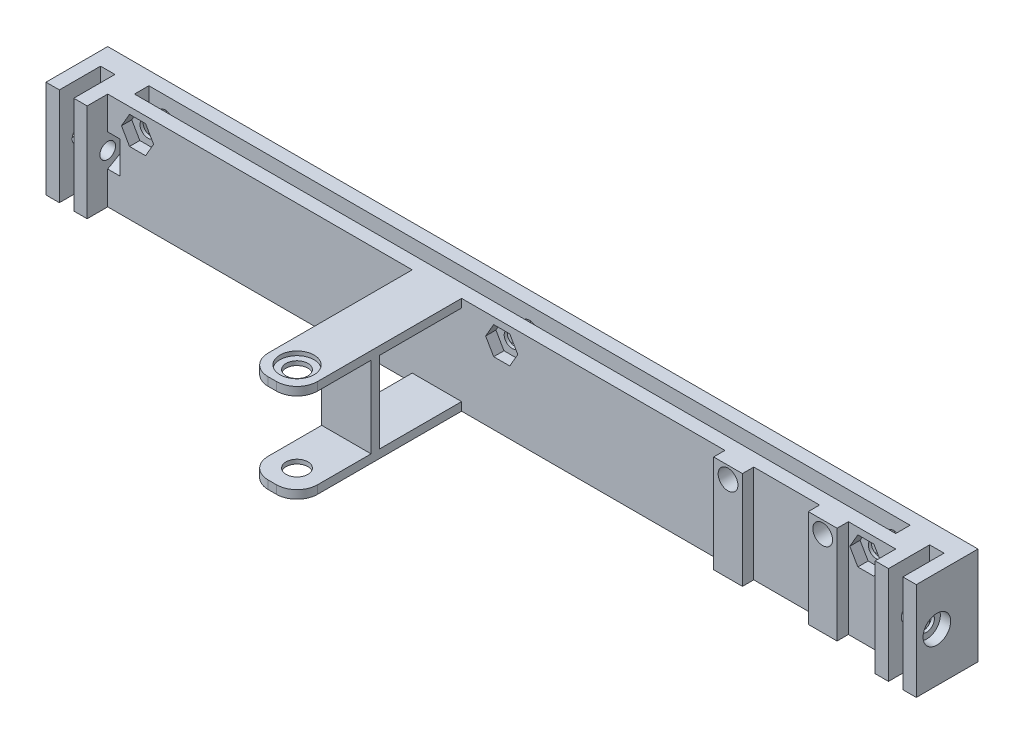
SolidWorks part; units mm, degrees
ref_plane "Front Plane" through (0, 0, 0) normal (1, 0, 0) x (0, 1, 0)
ref_plane "Top Plane" through (0, 0, 0) normal (0, 0, 1) x (0, 1, 0)
ref_plane "Right Plane" through (0, 0, 0) normal (0, 1, 0) x (-1, 0, 0)
sketch "Sketch2" plane through (0, 0, 0) normal (0, 0, 1) x (0, 1, 0)
  line L1 (-71.25, 0) -> (-95, 0)
  line L2 (-71.25, 0) -> (-71.25, 12)
  line L3 (-71.25, 12) -> (-95, 12)
  line L4 (-95, 0) -> (-95, 12)
extrude "Boss-Extrude1" add sketch "Sketch2" along normal blind 10
sketch "Sketch3" plane through (0, 0, 10) normal (0, 0, 1) x (1, 0, 0)
  line L1 (-12, -71.25) -> (0, -71.25)
  line L2 (-12, -71.25) -> (-12, -73.275)
  line L3 (-12, -73.275) -> (0, -73.275)
  line L4 (0, -71.25) -> (0, -73.275)
  line L6 (-12, -73.275) -> (0, -73.275) construction
  dimension "D1" = 2.025
extrude "Boss-Extrude2" add sketch "Sketch3" along normal blind 40
fillet "Fillet1" radius 5 2 edges at (0, -72.2625, 50) (-12, -72.2625, 50)
ref_plane "Plane1" through (0, -83.125, 0) normal (0, 1, 0) x (1, 0, 0)
mirror "Mirror1" about plane through (0, -83.125, 0) normal (0, 1, 0) of "Fillet1", "Boss-Extrude2"
sketch "Sketch5" plane through (0, -95, 0) normal (0, -1, 0) x (1, 0, 0)
  line L1 (-6, 50) -> (-12, 50)
  line L2 (-6, 50) -> (-6, 44)
  line L3 (-6, 44) -> (-12, 44)
  line L4 (-12, 50) -> (-12, 44)
  line L5 (-5, 50) -> (-7, 50) construction
  line L6 (-12, 45) -> (-12, 0) construction
  circle A0 centre (-6, 44) radius 2.65
  dimension "D2" = 5.3
  dimension "D1" = 6
extrude "Cut-Extrude1" cut sketch "Sketch5" against normal through all contours A0
sketch "Sketch6" plane through (0, -95, 0) normal (0, -1, 0) x (1, 0, 0)
  line L1 (-6, 50) -> (-12, 50)
  line L2 (-6, 50) -> (-6, 44)
  line L3 (-6, 44) -> (-12, 44)
  line L4 (-12, 50) -> (-12, 44)
  line L6 (-5, 50) -> (-7, 50) construction
  line L7 (-12, 45) -> (-12, 0) construction
  circle A0 centre (-6, 44) radius 4.15
  dimension "D1" = 6
  dimension "D2" = 8.3
extrude "Cut-Extrude2" cut sketch "Sketch6" against normal blind 1 contours A0
mirror "Mirror2" about plane through (0, -83.125, 0) normal (0, 1, 0) of "Cut-Extrude2"
sketch "Sketch7" plane through (0, 0, 0) normal (0, 0, -1) x (1, 0, 0)
  line L1 (-6, 95) -> (-96, 95)
  line L2 (-6, 95) -> (-6, 71.25)
  line L3 (-6, 71.25) -> (-96, 71.25)
  line L4 (-96, 95) -> (-96, 71.25)
  line L5 (-6, 95) -> (115.5, 95)
  line L6 (-6, 95) -> (-6, 71.25)
  line L7 (-6, 71.25) -> (115.5, 71.25)
  line L8 (115.5, 95) -> (115.5, 71.25)
  line L10 (-12, 95) -> (0, 95) construction
  line L11 (0, 71.25) -> (-12, 71.25) construction
  line M20 (0, 71.25) -> (0, 95)
  line M22 (-12, 95) -> (-12, 71.25)
  dimension "D1" = 90
  dimension "D2" = 121.5
extrude "Boss-Extrude3" add sketch "Sketch7" against normal blind 10 contours L1 L4 L3 M22 | L8 L5 L7 M20 region at (-54, -83.125, 0) region at (57.75, -83.125, 0)
sketch "Sketch8" plane through (0, 0, 10) normal (0, 0, 1) x (1, 0, 0)
  line L1 (115.5, -71.25) -> (105.5, -71.25)
  line L2 (115.5, -71.25) -> (115.5, -95)
  line L3 (115.5, -95) -> (105.5, -95)
  line L4 (105.5, -71.25) -> (105.5, -95)
  line L6 (-96, -71.25) -> (-86, -71.25)
  line L7 (-96, -71.25) -> (-96, -95)
  line L8 (-96, -95) -> (-86, -95)
  line L9 (-86, -71.25) -> (-86, -95)
  dimension "D1" = 10
  dimension "D2" = 10
extrude "Boss-Extrude4" add sketch "Sketch8" along normal blind 5
sketch "Sketch10" plane through (-12, 0, 0) normal (-1, 0, 0) x (0, -1, 0)
  line L0 (95, 45) -> (95, 10) construction
  line L1 (71.25, 10) -> (95, 10)
  line L2 (71.25, 10) -> (71.25, 12)
  line L3 (71.25, 12) -> (95, 12)
  line L4 (95, 10) -> (95, 12)
  dimension "D1" = 2
extrude "Boss-Extrude5" [suppressed] add sketch "Sketch10" along normal blind 24
sketch "Sketch18" plane through (0, -71.25, 0) normal (0, 1, 0) x (-1, 0, 0)
  line L1 (0, 10) -> (12, 10)
  line L2 (0, 10) -> (0, 30)
  line L3 (0, 30) -> (12, 30)
  line L4 (12, 10) -> (12, 30)
  line L5 (12, 45) -> (12, 10) construction
  line L6 (0, 30) -> (12, 30)
  line L7 (0, 30) -> (0, 32)
  line L8 (0, 32) -> (12, 32)
  line L9 (12, 30) -> (12, 32)
  dimension "D1" = 20
  dimension "D2" = 2
extrude "Boss-Extrude7" add sketch "Sketch18" against normal through all contours L7 L6 L9 L8
sketch "Sketch11" plane through (0, -71.25, 0) normal (0, 1, 0) x (-1, 0, 0)
  line L1 (86, 0) -> (-105.5, 0)
  line L2 (86, 0) -> (86, 10)
  line L3 (86, 10) -> (-105.5, 10)
  line L4 (-105.5, 0) -> (-105.5, 10)
  line L5 (82.75, 6.75) -> (-102.25, 6.75)
  line L6 (-102.25, 3.25) -> (-102.25, 6.75)
  line L7 (82.75, 3.25) -> (-102.25, 3.25)
  line L8 (82.75, 3.25) -> (82.75, 6.75)
  line L12 (96, 0) -> (86, 0)
  line L13 (96, 0) -> (96, 10)
  line L14 (96, 10) -> (86, 10)
  line L15 (86, 0) -> (86, 10)
  dimension "D1" = 3.25
extrude "Cut-Extrude3" cut sketch "Sketch11" against normal blind 10 contours L7 L8 L5 L6 region at (9.75, -71.25, 5)
mirror "Mirror3" about plane through (0, -83.125, 0) normal (0, 1, 0) of "Cut-Extrude3"
sketch "Sketch12" plane through (0, 0, 10) normal (0, 0, 1) x (1, 0, 0)
  line L1 (-86, -71.25) -> (-78.75, -71.25)
  line L2 (-86, -71.25) -> (-86, -76.25)
  line L3 (-86, -76.25) -> (-78.75, -76.25)
  line L4 (-78.75, -71.25) -> (-78.75, -76.25)
  circle A0 centre (-78.75, -76.25) radius 1.9
  circle A1 centre (-78.75, -76.25) radius 3.15
  dimension "D3" = 3.8
  dimension "D4" = 6.3
  dimension "D1" = 7.25
extrude "Cut-Extrude4" cut sketch "Sketch12" against normal through all and the other way through all contours A0
sketch "Sketch15" plane through (0, 0, 0) normal (0, 0, 1) x (1, 0, 0)
  circle A0 centre (-78.75, -76.25) radius 3.35
  dimension "D1" = 6.7
extrude "Cut-Extrude5" cut sketch "Sketch15" along normal blind 2.5
sketch "Sketch16" plane through (0, 0, 10) normal (0, 0, 1) x (1, 0, 0)
  line L0 (-82.6541, -76.25) -> (-80.7021, -79.6311)
  line L1 (-82.25, -76.25) -> (-80.5, -79.2811)
  line L2 (-80.5, -79.2811) -> (-77, -79.2811)
  line L3 (-77, -79.2811) -> (-75.25, -76.25)
  line L4 (-75.25, -76.25) -> (-77, -73.2189)
  line L5 (-77, -73.2189) -> (-80.5, -73.2189)
  line L6 (-80.5, -73.2189) -> (-82.25, -76.25)
  line L7 (-80.7021, -79.6311) -> (-76.7979, -79.6311)
  line L8 (-76.7979, -79.6311) -> (-74.8459, -76.25)
  line L9 (-74.8459, -76.25) -> (-76.7979, -72.8689)
  line L10 (-76.7979, -72.8689) -> (-80.7021, -72.8689)
  line L11 (-80.7021, -72.8689) -> (-82.6541, -76.25)
  line L12 (-12, -71.25) -> (-86, -71.25) construction
  circle A0 centre (-78.75, -76.25) radius 3.0311 construction
  circle M23 centre (-78.75, -76.25) radius 1.9
  dimension "D2" = 0.35
extrude "Cut-Extrude6" cut sketch "Sketch16" against normal blind 2.5 contours L10 L11 L0 L7 L8 L9 L6 L5 L4 L3 L2 L1 | L5 L6 L1 L2 L3 L4 M23 region at (-81.5887, -74.6111, 10) region at (-81.2948, -74.7808, 10)
pattern_linear "LPattern1" count 3 spacing 88.5 along (1, 0, 0) of "Cut-Extrude4", "Cut-Extrude6", "Cut-Extrude5"
sketch "Sketch14" plane through (0, 0, 10) normal (0, 0, 1) x (1, 0, 0)
  line L0 (0, -95) -> (105.5, -95) construction
  line L1 (105.5, -71.25) -> (94, -71.25)
  line L2 (105.5, -71.25) -> (105.5, -95)
  line L3 (105.5, -95) -> (94, -95)
  line L4 (94, -71.25) -> (94, -95)
  line L6 (94, -71.25) -> (87, -71.25)
  line L7 (94, -71.25) -> (94, -95)
  line L8 (94, -95) -> (87, -95)
  line L9 (87, -71.25) -> (87, -95)
  line L10 (87, -71.25) -> (71, -71.25)
  line L11 (87, -71.25) -> (87, -95)
  line L12 (87, -95) -> (71, -95)
  line L13 (71, -71.25) -> (71, -95)
  line L14 (71, -71.25) -> (64, -71.25)
  line L15 (71, -71.25) -> (71, -95)
  line L16 (71, -95) -> (64, -95)
  line L17 (64, -71.25) -> (64, -95)
  line M22 (105.5, -71.25) -> (0, -71.25)
  line M24 (0, -95) -> (105.5, -95)
  dimension "D1" = 11.5
  dimension "D2" = 7
  dimension "D3" = 16
  dimension "D4" = 7
extrude "Boss-Extrude6" add sketch "Sketch14" along normal blind 2.75 contours L17 L13 M22 M24 | L9 L4 M22 M24 region at (90.5, -83.125, 10) region at (67.5, -83.125, 10)
sketch "Sketch19" plane through (0, -83.125, 0) normal (0, 1, 0) x (1, 0, 0)
  line L1 (0, -10) -> (40, -10)
  line L2 (0, -10) -> (0, -37)
  line L3 (0, -37) -> (40, -37)
  line L4 (40, -10) -> (40, -37)
  dimension "D1" = 27
  dimension "D2" = 40
extrude "Boss-Extrude8" [suppressed] add sketch "Sketch19" against normal blind 1 and the other way blind 1
sketch "Sketch21" plane through (0, -71.25, 0) normal (0, 1, 0) x (-1, 0, 0)
  line L0 (-112.25, 5) -> (-108.75, 5)
  line L1 (-115.5, 15) -> (-112.25, 15)
  line L2 (-115.5, 15) -> (-115.5, 5)
  line L3 (-115.5, 5) -> (-112.25, 5)
  line L4 (-112.25, 15) -> (-112.25, 5)
  line L5 (-105.5, 15) -> (-108.75, 15)
  line L6 (-105.5, 15) -> (-105.5, 5)
  line L7 (-105.5, 5) -> (-108.75, 5)
  line L8 (-108.75, 15) -> (-108.75, 5)
  line M22 (-105.5, 15) -> (-115.5, 15)
  dimension "D1" = 10
  dimension "D2" = 3.25
  dimension "D3" = 3.25
  dimension "D4" = 10
extrude "Cut-Extrude7" cut sketch "Sketch21" against normal up to next contours L8 L4 L0 M22 region at (110.5, -71.25, 10)
pattern_linear "LPattern2" count 2 spacing 201.5 along (-1, 0, 0) of "Cut-Extrude7"
sketch "Sketch22" plane through (0, 0, 12.75) normal (0, 0, 1) x (1, 0, 0)
  line L1 (94, -71.25) -> (90.5, -71.25)
  line L2 (94, -71.25) -> (94, -74.25)
  line L3 (94, -74.25) -> (90.5, -74.25)
  line L4 (90.5, -71.25) -> (90.5, -74.25)
  circle A0 centre (90.5, -74.25) radius 2.4
extrude "Cut-Extrude8" cut sketch "Sketch22" against normal blind 3.8 contours A0
sketch "Sketch26" plane through (0, 0, 8.95) normal (0, 0, 1) x (1, 0, 0)
  circle A0 centre (90.5, -74.25) radius 1.75
extrude "Cut-Extrude12" cut sketch "Sketch26" against normal blind 0.6 contours A0
pattern_linear "LPattern3" count 2 spacing 23 along (-1, 0, 0) of "Cut-Extrude8", "Cut-Extrude12"
sketch "Sketch23" plane through (115.5, 0, 0) normal (1, 0, 0) x (0, 1, 0)
  line L0 (-95, 15) -> (-71.25, 15) construction
  line L1 (-95, 15) -> (-83.125, 15)
  line L2 (-95, 15) -> (-95, 10)
  line L3 (-95, 10) -> (-83.125, 10)
  line L4 (-83.125, 15) -> (-83.125, 10)
  circle A0 centre (-83.125, 10) radius 1.9
  dimension "D2" = 3.8
  dimension "D1" = 5
extrude "Cut-Extrude9" cut sketch "Sketch23" against normal blind 10 contours A0
sketch "Sketch24" plane through (115.5, 0, 0) normal (1, 0, 0) x (0, 1, 0)
  circle A0 centre (-83.125, 10) radius 3.35
  dimension "D1" = 6.7
extrude "Cut-Extrude10" cut sketch "Sketch24" against normal blind 2.5
sketch "Sketch25" plane through (105.5, 0, 0) normal (-1, 0, 0) x (0, -1, 0)
  line L0 (71.25, 15) -> (95, 15) construction
  line L1 (81.375, 13.0311) -> (79.625, 10)
  line L2 (79.625, 10) -> (81.375, 6.9689)
  line L3 (81.375, 6.9689) -> (84.875, 6.9689)
  line L4 (84.875, 6.9689) -> (86.625, 10)
  line L5 (86.625, 10) -> (84.875, 13.0311)
  line L6 (84.875, 13.0311) -> (81.375, 13.0311)
  line L7 (81.1729, 13.3811) -> (79.2209, 10)
  line L8 (79.2209, 10) -> (81.1729, 6.6189)
  line L9 (81.1729, 6.6189) -> (85.0771, 6.6189)
  line L10 (85.0771, 6.6189) -> (87.0291, 10)
  line L11 (87.0291, 10) -> (85.0771, 13.3811)
  line L12 (85.0771, 13.3811) -> (81.1729, 13.3811)
  circle A0 centre (83.125, 10) radius 3.0311 construction
  dimension "D2" = 0.35
extrude "Cut-Extrude11" cut sketch "Sketch25" along normal blind 3 contours L11 L12 L7 L8 L9 L10
ref_plane "Plane2" through (9.75, 0, 0) normal (1, 0, 0) x (0, 0, -1)
mirror "Mirror4" about plane through (9.75, 0, 0) normal (1, 0, 0) of "Cut-Extrude9", "Cut-Extrude11", "Cut-Extrude10"
equation "\"whitekey_cutout_length\"= 101.5"
equation "\"wall_thickness\"=10"
equation "\"base_mount_height\"=40"
equation "\"D1@Boss-Extrude2\"=\"base_mount_height\""
equation "\"D1@Sketch7\"=\"base_rear_length\"+\"wall_thickness\""
equation "\"D2@Sketch7\"=\"wall_thickness\"+\"base_front_length\""
equation "\"base_rear_length\"=80"
equation "\"D1@Boss-Extrude3\"=\"wall_thickness\""
equation "\"D1@Sketch8\"=\"wall_thickness\""
equation "\"D2@Sketch8\"=\"wall_thickness\""
equation "\"dowel_recess_offset\"=3.25"
equation "\"D1@Sketch11\"=\"dowel_recess_offset\""
equation "\"dowel_recess_depth\"=10"
equation "\"D1@Cut-Extrude3\"=\"dowel_recess_depth\""
equation "\"guide_brace_height\"=20"
equation "\"D1@Sketch18\"=\"guide_brace_height\""
equation "\"guide_brace_thickness\"=2"
equation "\"D2@Sketch18\"=\"guide_brace_thickness\""
equation "\"D3@LPattern1\"=0.5*(\"base_front_length\"+\"base_rear_length\"-\"screw_hole_wall_offset\"*2)"
equation "\"base_front_length\"=111.5"
equation "\"screw_hole_wall_offset\"=7.25"
equation "\"screw_hole_edge_inset\"=\"dowel_recess_depth\"/2"
equation "\"D1@Sketch12\"=\"screw_hole_wall_offset\""
equation "\"D2@Sketch12\"=\"screw_hole_edge_inset\""
equation "\"screw_hole_diameter\"=3.8"
equation "\"screw_head_hole_diameter\"=6.7"
equation "\"screw_nut_hole_side_len\"=3.5"
equation "\"D3@Sketch12\"=\"screw_hole_diameter\""
equation "\"D1@Sketch15\"=\"screw_head_hole_diameter\""
equation "\"D1@Sketch16\"=\"screw_nut_hole_side_len\""
equation "\"D1@Boss-Extrude6\"=6-\"dowel_recess_offset\""
equation "\"D1@Sketch21\"=\"dowel_recess_depth\""
equation "\"D2@Sketch21\"=\"dowel_recess_offset\""
equation "\"D3@Sketch21\"=\"dowel_recess_offset\""
equation "\"D4@Sketch21\"=\"dowel_recess_depth\""
equation "\"D3@LPattern2\"=\"base_front_length\"+\"base_rear_length\"+\"wall_thickness\""
equation "\"key_mount_recess_length\"=50"
equation "\"key_mount_recess_height\"=12.5"
equation "\"key_mount_recess_depth\"=1.5"
equation "\"screw_shaft_diameter\"=3.5"
equation "\"switch_board_width\"=30"
equation "\"D2@Sketch14\"=\"screw_shaft_diameter\"*2"
equation "\"D4@Sketch14\"=\"screw_shaft_diameter\"*2"
equation "\"D3@Sketch14\"=\"switch_board_width\"-\"screw_shaft_diameter\"*4"
equation "\"heatset_insert_hole_diameter\"=4.8"
equation "\"heatset_insert_hole_depth\"=3.8"
equation "\"D2@Sketch22\"=\"heatset_insert_hole_diameter\""
equation "\"D1@Cut-Extrude8\"=\"heatset_insert_hole_depth\""
equation "\"D3@LPattern3\"=\"switch_board_width\"-\"screw_shaft_diameter\"*2"
equation "\"switch_board_wall_offset\"=11.5"
equation "\"D1@Sketch14\"=\"switch_board_wall_offset\""
equation "\"D1@Sketch23\"=\"screw_hole_edge_inset\""
equation "\"D2@Sketch23\"=\"screw_hole_diameter\""
equation "\"D1@Sketch24\"=\"screw_head_hole_diameter\""
equation "\"screw_head_and_nut_recess_depth\"=2.5"
equation "\"D1@Cut-Extrude5\"=\"screw_head_and_nut_recess_depth\""
equation "\"D1@Cut-Extrude6\"=\"screw_head_and_nut_recess_depth\""
equation "\"D1@Cut-Extrude10\"=\"screw_head_and_nut_recess_depth\""
equation "\"D1@Sketch25\"=\"screw_nut_hole_side_len\""
equation "\"screw_nut_recess_offset\"=0.35"
equation "\"D2@Sketch16\"=\"screw_nut_recess_offset\""
equation "\"D2@Sketch25\"=\"screw_nut_recess_offset\""
equation "\"D1@Cut-Extrude11\"=\"screw_head_and_nut_recess_depth\"+0.5"
equation "\"D1@Cut-Extrude9\"=\"wall_thickness\""
equation "\"D1@Sketch26\"=\"screw_shaft_diameter\""
equation "\"switch_board_thickness\"=1.6"
equation "\"front_rear_panel_width\"=23.75"
equation "\"rod_length_adj\"=0.5"
equation "\"rod_insert_length\"=2.8"
equation "\"D1@Cut-Extrude12\"=6-\"heatset_insert_hole_depth\"-\"switch_board_thickness\""
equation "\"rod_diameter\"=5"
equation "\"rod_head_diameter\"=8"
equation "\"switch_black_key_mount_height\"=8"
equation "\"switch_white_key_mount_height\"=3"
equation "\"D2@Sketch5\"=\"rod_diameter\"+0.3"
equation "\"D2@Sketch6\"=\"rod_head_diameter\"+0.3"
equation "\"D1@Boss-Extrude4\"=\"wall_thickness\"/2"
